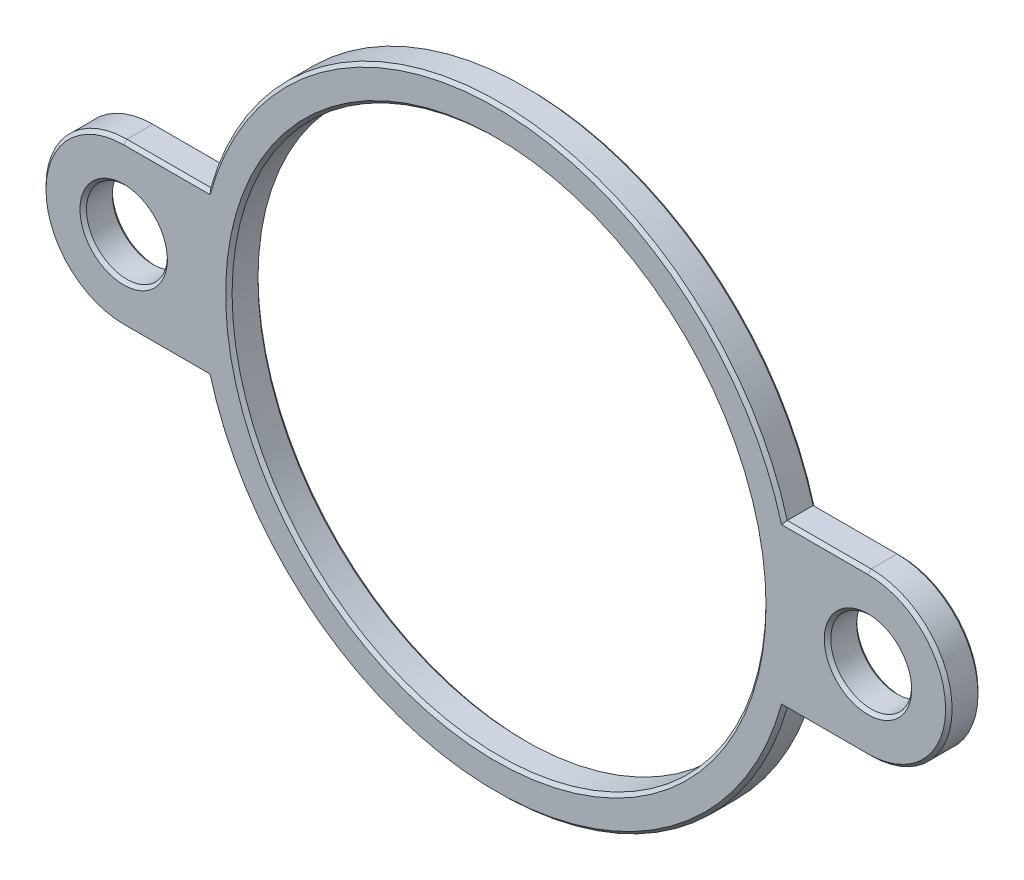
SolidWorks part; units mm, degrees
ref_plane "Спереди" through (0, 0, 0) normal (0, 0, 1) x (1, 0, 0)
ref_plane "Сверху" through (0, 0, 0) normal (0, 1, 0) x (1, 0, 0)
ref_plane "Справа" through (0, 0, 0) normal (1, 0, 0) x (0, 0, -1)
sketch "Эскиз1" plane through (0, 0, 0) normal (0, 0, 1) x (1, 0, 0)
  line L0 (23, 5) -> (17.8115, 5)
  line L1 (23, -5) -> (17.8115, -5)
  line L2 (0, 0) -> (0, 50000) construction
  line L3 (-23, -5) -> (-17.8115, -5)
  line L4 (-23, 5) -> (-17.8115, 5)
  arc A0 (17.8115, 5) -> (-17.8115, 5) centre (0, 0) ccw
  circle A1 centre (23, 0) radius 2.5
  arc A2 (23, 5) -> (23, -5) centre (23, 0) cw
  arc A3 (-23, 5) -> (-23, -5) centre (-23, 0) ccw
  circle A4 centre (-23, 0) radius 2.5
  arc A5 (-17.8115, -5) -> (17.8115, -5) centre (0, 0) ccw
  circle A6 centre (0, 0) radius 16.5
  dimension "D1" = 37
  dimension "D2" = 5
  dimension "D4" = 5
  dimension "D7" = 33
  dimension "D3" = 23
  dimension "D5" = 23
  dimension "D6" = 23
extrude "Бобышка-Вытянуть1" add sketch "Эскиз1" along normal blind 2
chamfer "Фаска2" distance 0.2 angle 45 22 edges at (16.5, 0, 2) (-25.5, 0, 2) (25.5, 0, 2) (20.4058, -5, 2) (0, -18.5, 2) (-20.4058, -5, 2) (-28, 0, 2) (-20.4058, 5, 2) (0, 18.5, 2) (20.4058, 5, 2) (28, 0, 2) (16.5, 0, 0) (25.5, 0, 0) (20.4058, 5, 0) (0, 18.5, 0) (-20.4058, 5, 0) (-28, 0, 0) (-20.4058, -5, 0) (0, -18.5, 0) (20.4058, -5, 0) (28, 0, 0) (-25.5, 0, 0)
